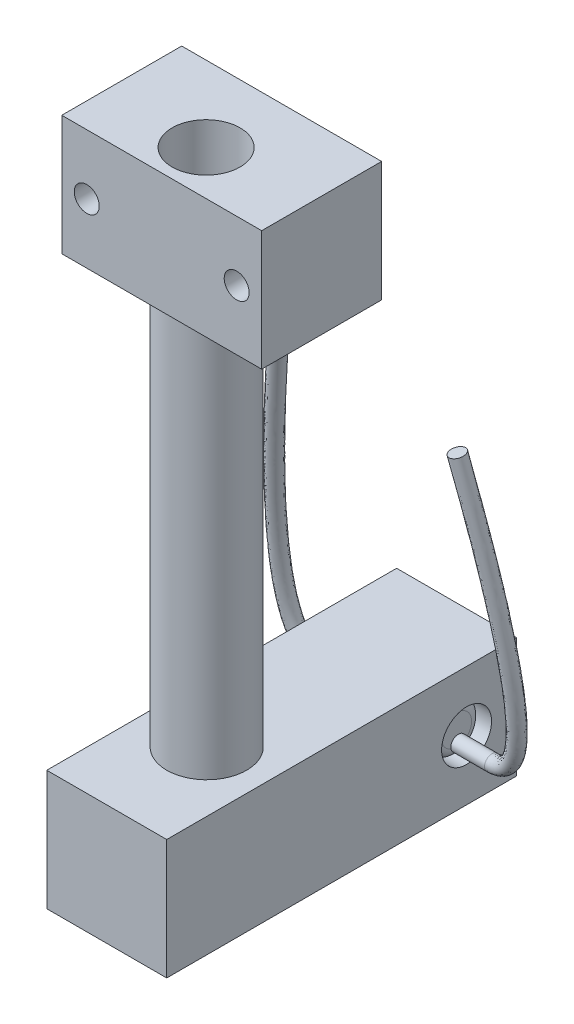
SolidWorks part; units mm, degrees
other "Alu-D8"
other "Alu-12x12"
other "PEEK-D8"
other "8-Omx6Wt"
material "PE mit sehr geringer Dichte PE (SS)"
material "3.0205 (EN AW-1200)"
ref_plane "Ebene vorne" through (0, 0, 0) normal (0, 0, 1) x (1, 0, 0)
ref_plane "Ebene oben" through (0, 0, 0) normal (0, 1, 0) x (1, 0, 0)
ref_plane "Ebene rechts" through (0, 0, 0) normal (1, 0, 0) x (0, 0, -1)
sketch "Skizze1" plane through (0, 0, 0) normal (0, 0, 1) x (1, 0, 0)
  line L1 (6, -6) -> (-6, -6)
  line L2 (6, -6) -> (6, 6)
  line L3 (6, 6) -> (-6, 6)
  line L4 (-6, -6) -> (-6, 6)
  line L5 (6, -6) -> (-6, 6) construction
  line L6 (6, 6) -> (-6, -6) construction
  point P0 (0, 0)
  dimension "D1" = 12
extrude "Aufsatz-Linear austragen1" add sketch "Skizze1" along normal blind 35
sketch "Skizze2" plane through (-6, 0, 0) normal (-1, 0, 0) x (0, 0, 1)
  line L0 (0, 6) -> (0, -6) construction
  circle A0 centre (5, 0) radius 2.5
  point P2 (0, 0)
  dimension "D1" = 5
  dimension "D2" = 5
extrude "Schnitt-Linear austragen1" cut sketch "Skizze2" against normal blind 35
hole_wizard "M8 Gewindebohrung1" positions "Skizze5" profile "Skizze4" tap size "M8" standard "DIN" end condition through all
sketch "Skizze5" plane through (0, 6, 0) normal (0, 1, 0) x (-1, 0, 0)
  line L0 (-6, 35) -> (6, 35) construction
  point P0 (0, 25)
  point P4 (0, 35)
  dimension "D1" = 10
sketch "Skizze4" plane through (0, 6, 25) normal (1, 0, 0) x (0, 0, 1)
  line L0 (0, 0) -> (0, 12)
  line L1 (0, 12) -> (3.4, 12)
  line L2 (3.4, 12) -> (3.4, 0)
  line L5 (3.4, 0) -> (0, 0)
  line L11 (0, -6.35) -> (0, 107.95) construction
  dimension "Bohrerdurchmesser" = 6.8
  dimension "Bohrungstiefe" = 12
cosmetic thread "Bohrungsgewinde1"
sketch "Skizze7" plane through (0, 0, 0) normal (1, 0, 0) x (0, 0, -1)
  line L0 (-25, 2) -> (-25, -10) construction
  line L1 (-25, -10) -> (-29, -10) construction
  line L2 (-29, 2) -> (-26.5, 2)
  line L3 (-29, -10) -> (-29, 2)
  line L4 (-29, 2) -> (-25, 2) construction
  line L5 (-35, -6) -> (0, -6) construction
  line L6 (-26.5, 2) -> (-26.5, -8.5)
  line L7 (-26.5, -8.5) -> (-25.25, -8.5)
  line L8 (-25.25, -8.5) -> (-25.25, -10)
  line L9 (-25.25, -10) -> (-29, -10)
  dimension "D1" = 8
  dimension "D2" = 8
  dimension "D3" = 12
  dimension "D4" = 0.5
  dimension "D5" = 3
  dimension "D6" = 1.5
revolve "Rotation1" add sketch "Skizze7" angle 360 about L0
cosmetic thread "Gewindedarstellung1"
chamfer "Fase1" distance 3 angle 45 1 edges at (0, -10, 29)
fillet "Verrundung2" radius 1 1 edges at (0, -7, 21)
sketch "Skizze8" plane through (0, 2, 0) normal (0, 1, 0) x (1, 0, 0)
  circle A0 centre (0, -25) radius 2.5
  circle A1 centre (0, -25) radius 4
  circle A2 centre (0, -25) radius 4
  dimension "D2" = 5
  dimension "D1" = 0
extrude "Aufsatz-Linear austragen2" add sketch "Skizze8" along normal blind 50 separate body
cosmetic thread "Gewindedarstellung2"
chamfer "Fase2" distance 1 angle 45 2 edges at (0, 2, 29) (0, 52, 29)
sketch "Skizze9" plane through (0, 0, 0) normal (1, 0, 0) x (0, 0, -1)
  circle A0 centre (-5, 0) radius 2.5
  dimension "D1" = 5
extrude "Aufsatz-Linear austragen3" add sketch "Skizze9" along normal mid plane 10 separate body
fillet "Verrundung3" radius 1 2 edges at (5, 0, 2.5) (-5, 0, 2.5)
ref_axis "Achse1" through (6, 0, 5) along (-1, 0, 0)
ref_plane "Ebene1" through (0, -0.6891, 4.9032) normal (0, 0.1392, -0.9903) x (-1, 0, 0)
sketch "Skizze10" plane through (0, -0.6891, 4.9032) normal (0, 0.1392, -0.9903) x (-1, 0, 0)
  line L0 (-8.3745, -0.5306) -> (8.3745, -0.5306)
  line L1 (0, -0.5306) -> (0, 6.0164) construction
  spline S0 degree 2 poles (8.3745, -0.5306) (14.661, -0.5306) (9.0031, 28.9529) knots 0 0 0 1 1 1
  spline S1 degree 2 poles (-8.3745, -0.5306) (-14.661, -0.5306) (-9.0031, 28.9529) knots 0 0 0 1 1 1
ref_plane "Ebene2" through (9.0031, 27.9821, 8.9326) normal (-0.1885, 0.9725, 0.1367) x (-0.9804, -0.1781, -0.0844)
sketch "Skizze11" plane through (9.0031, 27.9821, 8.9326) normal (-0.1885, 0.9725, 0.1367) x (-0.9804, -0.1781, -0.0844)
  circle A0 centre (0, 0) radius 0.75
  dimension "D1" = 1.5
sweep "Austragung1" add profiles "Skizze11" path "Skizze10"
sketch "Skizze12" plane through (0, 0, 0) normal (1, 0, 0) x (0, 0, -1)
  line L1 (-17.5, 46) -> (-29.5, 46)
  line L2 (-17.5, 46) -> (-17.5, 58)
  line L3 (-17.5, 58) -> (-29.5, 58)
  line L4 (-29.5, 46) -> (-29.5, 58)
  line L6 (-25, 58) -> (-25, 46) construction
  line L7 (-22, 52) -> (-28, 52) construction
  point P6 (-25, 52)
  dimension "D1" = 12
  dimension "D2" = 4.5
extrude "Aufsatz-Linear austragen4" add sketch "Skizze12" along normal mid plane 20 separate body
hole_wizard "M8 Gewindebohrung2" positions "Skizze14" profile "Skizze13" tap size "M8" standard "DIN"
sketch "Skizze14" plane through (0, 58, 0) normal (0, 1, 0) x (-1, 0, 0)
  point P0 (-0.0061, 25.0669)
sketch "Skizze13" plane through (0.0061, 58, 25.0669) normal (1, 0, 0) x (0, 0, 1)
  line L0 (0, 0) -> (0, 24.2929)
  line L1 (0, 24.2929) -> (3.4, 22.25)
  line L2 (3.4, 22.25) -> (3.4, 0)
  line L5 (3.4, 0) -> (0, 0)
  line L10 (0, 24.2929) -> (-3.4, 22.25) construction
  line L11 (0, -6.35) -> (0, 107.95) construction
  dimension "Bohrerdurchmesser" = 6.8
  dimension "Bohrungstiefe" = 22.25
  dimension "Spitzenwinkel" = 118
cosmetic thread "Bohrungsgewinde2"
hole_wizard "M3 Gewindebohrung1" positions "Skizze16" profile "Skizze15" tap size "M3" standard "DIN" end condition through all
sketch "Skizze16" plane through (0, 0, 17.5) normal (0, 0, -1) x (-1, 0, 0)
  line L0 (-7.5, 52) -> (7.5, 52) construction
  line L2 (0, 58) -> (0, 52) construction
  line L3 (-10, 58) -> (10, 58) construction
  line L5 (-10, 46) -> (-10, 58) construction
  point P0 (-7.5, 52)
  point P1 (7.5, 52)
  point P18 (-10, 52)
  dimension "D1" = 15
sketch "Skizze15" plane through (7.5, 52, 17.5) normal (1, 0, 0) x (0, 1, 0)
  line L0 (0, 0) -> (0, 17.5)
  line L1 (0, 17.5) -> (1.25, 17.5)
  line L2 (1.25, 17.5) -> (1.25, 0)
  line L5 (1.25, 0) -> (0, 0)
  line L11 (0, -6.35) -> (0, 107.95) construction
  dimension "Bohrerdurchmesser" = 2.5
  dimension "Bohrungstiefe" = 17.5
cosmetic thread "Bohrungsgewinde3"
cosmetic thread "Bohrungsgewinde4"
